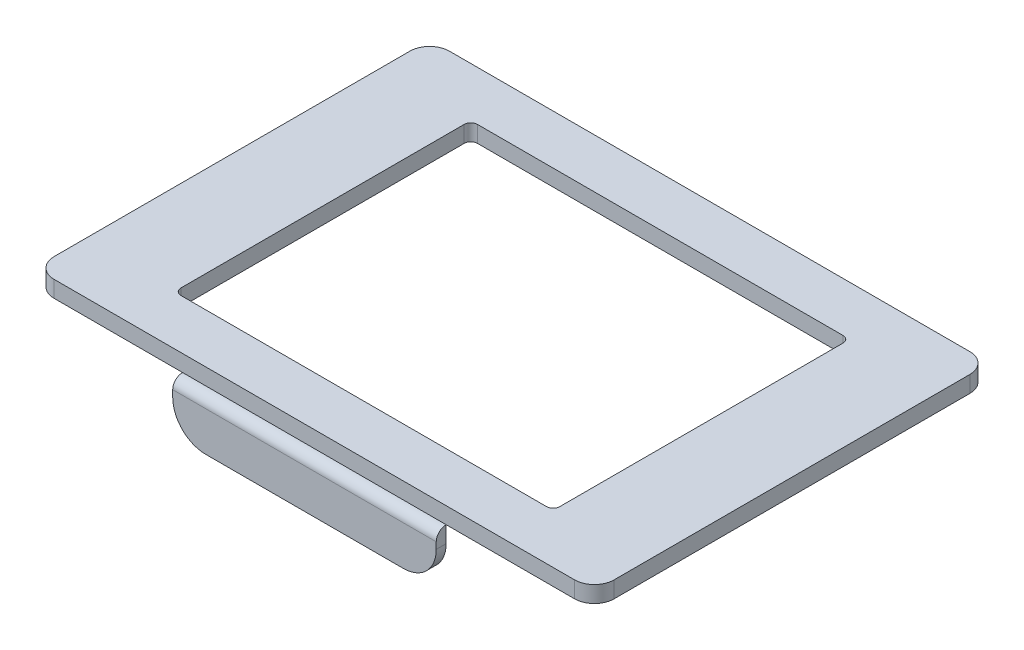
SolidWorks part; units mm, degrees
material "ABS PC"
ref_plane "Front Plane" through (0, 0, 0) normal (0, 0, 1) x (1, 0, 0)
ref_plane "Top Plane" through (0, 0, 0) normal (0, 1, 0) x (1, 0, 0)
ref_plane "Right Plane" through (0, 0, 0) normal (1, 0, 0) x (0, 0, -1)
sketch "Sketch1" plane through (0, 0, 0) normal (0, 1, 0) x (1, 0, 0)
  line L1 (-85, 60) -> (85, 60)
  line L2 (-85, 60) -> (-85, -60)
  line L3 (-85, -60) -> (85, -60)
  line L4 (85, 60) -> (85, -60)
  line L5 (-85, 60) -> (85, -60) construction
  line L6 (-85, -60) -> (85, 60) construction
  point P0 (0, 0)
  dimension "D1" = 170
  dimension "D2" = 120
extrude "Boss-Extrude1" add sketch "Sketch1" along normal blind 5
fillet "Fillet1" radius 6 4 edges at (85, 2.5, -60) (-85, 2.5, -60) (-85, 2.5, 60) (85, 2.5, 60)
sketch "Sketch2" plane through (0, 5, 0) normal (0, 1, 0) x (1, 0, 0)
  line L1 (-57.5, 45) -> (57.5, 45)
  line L2 (-57.5, 45) -> (-57.5, -45)
  line L3 (-57.5, -45) -> (57.5, -45)
  line L4 (57.5, 45) -> (57.5, -45)
  line L5 (-57.5, 45) -> (57.5, -45) construction
  line L6 (-57.5, -45) -> (57.5, 45) construction
  point P0 (0, 0)
  dimension "D1" = 90
  dimension "D2" = 115
extrude "Cut-Extrude1" cut sketch "Sketch2" against normal blind 10
fillet "Fillet2" radius 2 4 edges at (-57.5, 2.5, 45) (57.5, 2.5, 45) (57.5, 2.5, -45) (-57.5, 2.5, -45)
sketch "Sketch3" plane through (0, 0, 60) normal (0, 0, 1) x (1, 0, 0)
  line L0 (-79, 0) -> (79, 0) construction
  line L1 (-40, 0) -> (40, 0)
  line L2 (-40, 0) -> (-40, -15)
  line L3 (-40, -15) -> (40, -15)
  line L4 (40, 0) -> (40, -15)
  line L5 (0, 0) -> (0, -15) construction
  dimension "D1" = 80
  dimension "D2" = 15
extrude "Boss-Extrude2" add sketch "Sketch3" along normal blind 3 separate body
fillet "Fillet3" radius 10 2 edges at (40, -15, 61.5) (-40, -15, 61.5)
fillet "Fillet4" radius 3 1 edges at (0, 0, 63)
sketch "Sketch4" plane through (0, 0, -60) normal (0, 0, -1) x (-1, 0, 0)
  line L1 (-40, 0) -> (40, 0)
  line L2 (-40, 0) -> (-40, -15)
  line L3 (-40, -15) -> (40, -15)
  line L4 (40, 0) -> (40, -15)
  dimension "D1" = 15
  dimension "D2" = 80
extrude "Boss-Extrude3" add sketch "Sketch4" along normal blind 3 separate body
fillet "Fillet5" radius 3 1 edges at (0, 0, -63)
fillet "Fillet6" radius 10 2 edges at (40, -15, -61.5) (-40, -15, -61.5)
